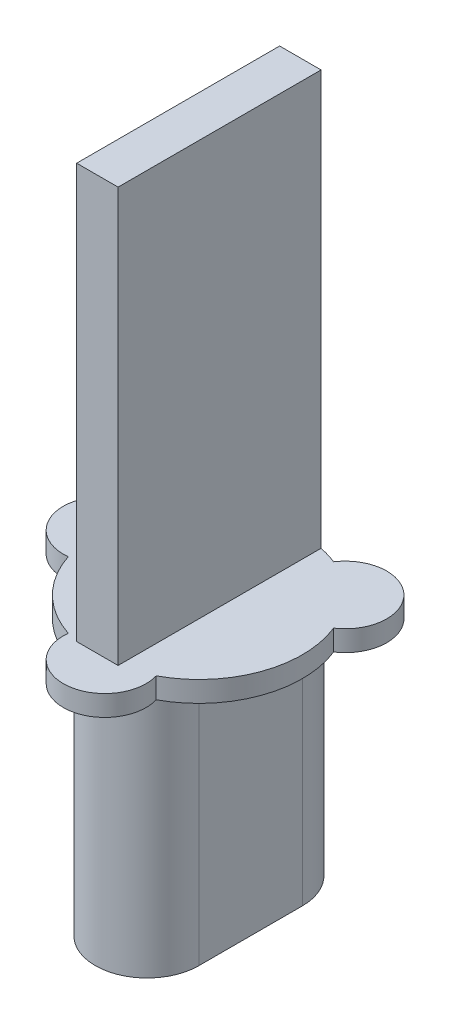
SolidWorks part; units mm, degrees
ref_plane "Front Plane" through (0, 0, 0) normal (0, 0, 1) x (1, 0, 0)
ref_plane "Top Plane" through (0, 0, 0) normal (0, 1, 0) x (1, 0, 0)
ref_plane "Right Plane" through (0, 0, 0) normal (1, 0, 0) x (0, 0, -1)
sketch "Sketch1" plane through (0, 0, 0) normal (0, 1, 0) x (1, 0, 0)
  line L0 (0, 2.5) -> (0, -2.5) construction
  line L1 (2.5, 2.5) -> (2.5, -2.5)
  line L2 (-2.5, 2.5) -> (-2.5, -2.5)
  line L3 (0.4358, -4.981) -> (-4.981, 0.4358) construction
  line L5 (-1, -4.899) -> (1, -4.899)
  line L6 (-1, -4.899) -> (-1, 4.899)
  line L7 (-1, 4.899) -> (1, 4.899)
  line L8 (1, -4.899) -> (1, 4.899)
  line L9 (-1, -4.899) -> (1, 4.899) construction
  line L10 (-1, 4.899) -> (1, -4.899) construction
  arc A1 (2.5, 2.5) -> (-2.5, 2.5) centre (0, 2.5) ccw
  arc A2 (-2.5, -2.5) -> (2.5, -2.5) centre (0, -2.5) ccw
  circle A3 centre (3.5355, 3.5355) radius 2
  circle A4 centre (-4.981, 0.4358) radius 2
  circle A5 centre (0.4358, -4.981) radius 2
  circle A6 centre (0, 0) radius 5
  point P3 (0, 0)
  point P9 (0, 5)
  point P10 (0, -5)
  point P18 (-2.2726, -2.2726)
  point P22 (0, 0)
  point P23 (2.5, 4.3331)
  point P24 (1.5355, 4.7581)
  point P25 (1.4527, 4.7843)
  dimension "D3" = 2.5
  dimension "D4" = 4
  dimension "D5" = 4
  dimension "D6" = 4
  dimension "D7" = 10
  dimension "D2" = 10
  dimension "D9" = 2
  dimension "D1" = 25
  dimension "D8" = 90
  dimension "key_angle_offset" = 45
extrude "Boss-Extrude1" add sketch "Sketch1" against normal blind 13 contours L2 A2 L1 A1
extrude "Boss-Extrude2" add sketch "Sketch1<3>" against normal blind 1 contours A6 A5 | A6 A4 | A6 A3 | A6 region at (4.0819, 0, -4.0819) region at (0.5031, 0, 5.7507) region at (-5.7507, 0, -0.5031)
sketch "Sketch1<3>" plane through (0, 0, 0) normal (0, 1, 0) x (1, 0, 0) same geometry as "Sketch1"
extrude "Boss-Extrude3" add sketch "Sketch1<5>" along normal blind 20 contours L6 L7 L8 L5
sketch "Sketch1<5>" plane through (0, 0, 0) normal (0, 1, 0) x (1, 0, 0) same geometry as "Sketch1"
equation "\"key_pin_length\"= 25.00mm"
equation "\"key_pin_dia\"= 20.00mm"
equation "\"driver_pin_travel\"= 3.00mm"
equation "\"driver_pin_dia\"= 0.3mm"
equation "\"driver_pin_neck_dia\"= 2.00mm"
equation "\"driver_pin_head_dia\" = 2mm"
equation "\"driver_pin_head_length\" = 2mm"
equation "\"plug_wall_thickness\" = 2mm"
equation "\"plug_spring_solid_length\"= 2mm"
equation "\"plug_length\"= 2 * \"key_pin_length\" + 2 * \"plug_wall_thickness\" + \"plug_spring_solid_length\""
equation "\"plug_dia\"= \"key_pin_dia\" + 2*(\"driver_pin_travel\" + 1mm + \"plug_spring_solid_length\" + 1mm)"
equation "\"true_gate_depth\" = 1.25mm"
equation "\"key_notches_dia\" = 4mm"
equation "\"D4@Sketch1\"=\"key_notches_dia\""
equation "\"D6@Sketch1\"=\"key_notches_dia\""
equation "\"D5@Sketch1\"=\"key_notches_dia\""
equation "\"key_notches_offset_angle\" = 25deg"
equation "\"D1@Sketch1\"=\"key_notches_offset_angle\""
